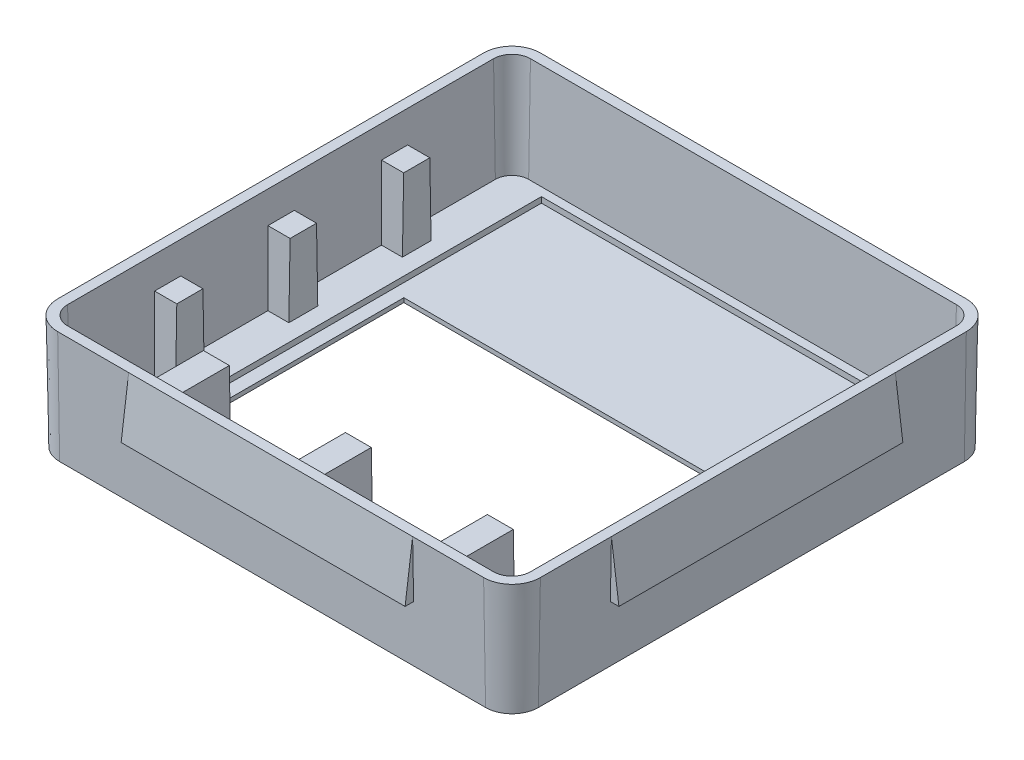
SolidWorks part; units mm, degrees
material "ABS"
ref_plane "Front Plane" through (0, 0, 0) normal (0, 0, 1) x (1, 0, 0)
ref_plane "Top Plane" through (0, 0, 0) normal (0, 1, 0) x (1, 0, 0)
ref_plane "Right Plane" through (0, 0, 0) normal (1, 0, 0) x (0, 0, -1)
sketch "Sketch1" plane through (0, 0, 0) normal (0, 1, 0) x (1, 0, 0)
  line L1 (-7.5, -8.5) -> (7.5, -8.5)
  line L2 (-8.5, -7.5) -> (-8.5, 7.5)
  line L3 (-7.5, 8.5) -> (7.5, 8.5)
  line L4 (8.5, -7.5) -> (8.5, 7.5)
  line L5 (-8.5, -8.5) -> (8.5, 8.5) construction
  line L6 (-8.5, 8.5) -> (8.5, -8.5) construction
  arc A0 (-8.5, 7.5) -> (-7.5, 8.5) centre (-7.5, 7.5) cw
  arc A1 (8.5, 7.5) -> (7.5, 8.5) centre (7.5, 7.5) ccw
  arc A2 (8.5, -7.5) -> (7.5, -8.5) centre (7.5, -7.5) cw
  arc A3 (-7.5, -8.5) -> (-8.5, -7.5) centre (-7.5, -7.5) cw
  point P0 (0, 0)
  dimension "D3" = 1
  dimension "D1" = 17
  dimension "D2" = 17
extrude "Boss-Extrude1" add sketch "Sketch1" against normal blind 4 draft 1
shell "Shell1" thickness 0.35 removed face at (0, 0, 0)
sketch "Sketch2" plane through (0, -4, 0) normal (0, -1, 0) x (1, 0, 0)
  line L0 (-7.5, 8.5) -> (7.5, 8.5) construction
  line L1 (-6.29, 4.5) -> (6.29, 4.5)
  line L2 (-6.29, 4.5) -> (-6.29, -2.48)
  line L3 (-6.29, -2.48) -> (6.29, -2.48)
  line L4 (6.29, 4.5) -> (6.29, -2.48)
  point P0 (0, 0)
  dimension "D1" = 4
  dimension "D2" = 6.98
extrude "Cut-Extrude1" cut sketch "Sketch2" against normal blind 2
sketch "Sketch3" plane through (0, -3.65, 0) normal (0, 1, 0) x (1, 0, 0)
  line L1 (6.75, 7.7862) -> (-6.75, 7.7862)
  line L2 (6.75, 7.7862) -> (6.75, -5.31)
  line L3 (6.75, -5.31) -> (-6.75, -5.31)
  line L4 (-6.75, 7.7862) -> (-6.75, -5.31)
  line L5 (6.29, 2.48) -> (6.29, -4.5) construction
  line L6 (-6.29, -4.5) -> (-6.29, 2.48) construction
  line L8 (6.29, -4.5) -> (-6.29, -4.5) construction
  line L9 (7.5, 8.0862) -> (-7.5, 8.0862) construction
  point P0 (0, 0)
  dimension "D1" = 0.81
  dimension "D2" = 0.46
  dimension "D3" = 0.46
  dimension "D4" = 0.3
extrude "Cut-Extrude2" cut sketch "Sketch3" against normal blind 0.2
ref_plane "Plane1" through (0, -1.2, 0) normal (0, -1, 0) x (-1, 0, 0)
ref_plane "Plane4" through (7.35, 0, 0) normal (-1, 0, 0) x (0, 0, 1)
sketch "Sketch11" plane through (7.35, 0, 0) normal (-1, 0, 0) x (0, 0, 1)
  line L0 (-9.35, -1.2) -> (9.35, -1.2) construction
  line L1 (-0.4555, -1.1) -> (0.4651, -1.1)
  line L3 (-0.5, -3.65) -> (0.5096, -3.65)
  line L5 (-7.5, -3.65) -> (7.5, -3.65) construction
  line L7 (0.5096, -3.65) -> (0.4651, -1.1)
  line L8 (-0.5, -3.65) -> (-0.4555, -1.1)
  dimension "D1" = 0.1
  dimension "D2" = 89
  dimension "D3" = 89
extrude "Boss-Extrude3" add sketch "Sketch11" against normal up to surface (0.7362 mm away) up to face at (8.1181, -1.825, 0)
ref_plane "Plane5" through (-7.35, 0, 0) normal (1, 0, 0) x (0, 0, -1)
sketch "Sketch13" plane through (-7.35, 0, 0) normal (1, 0, 0) x (0, 0, -1)
  line L0 (-9.35, -1.2) -> (9.35, -1.2) construction
  line L3 (-0.5, -3.65) -> (0.5096, -3.65)
  line L6 (0.5096, -3.65) -> (0.4651, -1.1)
  line L7 (-0.5, -3.65) -> (-0.4555, -1.1)
  line L8 (-0.4555, -1.1) -> (0.4651, -1.1)
  dimension "D1" = 0.1
  dimension "D2" = 89
  dimension "D3" = 89
extrude "Boss-Extrude4" add sketch "Sketch13" against normal up to surface (0.7362 mm away) up to face at (-8.1181, -1.825, 0)
ref_plane "Plane6" through (0, 0, 0) normal (1, 0, 0.0016) x (0.0016, 0, -1)
pattern_linear "LPattern2" count 2 spacing 4 along (0, 0, 1) of "Boss-Extrude3"
mirror "Mirror4" about plane through (0, 0, 0) normal (0, 0, 1) of "LPattern2"
pattern_linear "LPattern3" count 2 spacing 4 along (0, 0, 1) of "Boss-Extrude4"
mirror "Mirror5" about plane through (0, 0, 0) normal (0, 0, 1) of "LPattern3"
ref_plane "Plane7" through (0, 0, 5.41) normal (0, 0, 1) x (1, 0, 0)
sketch "Sketch16" plane through (0, 0, 5.41) normal (0, 0, 1) x (1, 0, 0)
  line L0 (-0.5, -3.65) -> (0.5, -3.65)
  line L1 (-7.5, -3.65) -> (7.5, -3.65) construction
  line L2 (0, -55) -> (0, 55) construction
  line L3 (-0.4555, -1.1) -> (0.4555, -1.1)
  line L5 (-0.5, -3.65) -> (-0.4555, -1.1)
  line L6 (0.5, -3.65) -> (0.4555, -1.1)
  line L7 (-9.35, -1.2) -> (9.35, -1.2) construction
  point P9 (0, -1.1)
  dimension "D1" = 0.5
  dimension "D2" = 0.5
  dimension "D3" = 89
  dimension "D4" = 89
  dimension "D5" = 0.1
extrude "Boss-Extrude5" add sketch "Sketch16" along normal up to surface (2.6762 mm away) up to face at (0, -1.825, 8.1181)
pattern_linear "LPattern4" count 2 spacing 5 along (1, 0, 0) of "Boss-Extrude5"
mirror "Mirror6" about plane through (0, 0, 0) normal (1, 0, 0) of "LPattern4"
sketch "Sketch17" plane through (0, 0, 0) normal (0, 0, 1) x (1, 0, 0)
  line L0 (-8.5, 0) -> (-8.4651, -2)
  line L1 (9.35, 0) -> (-9.35, 0) construction
  line L2 (-8.4302, -4) -> (-8.5, 0) construction
  line L3 (-8.4651, -2) -> (-8.7651, -2)
  line L4 (-8.7651, -2) -> (-8.5, 0)
  line L5 (-8.4302, -4) -> (-7.5, -4) construction
  line L6 (0, -2.2) -> (0, 2.2) construction
  line L7 (8.7651, -2) -> (8.5, 0)
  line L8 (8.4651, -2) -> (8.7651, -2)
  line L9 (8.5, 0) -> (8.4651, -2)
  dimension "D1" = 0.3
  dimension "D2" = 2
extrude "Boss-Extrude6" add sketch "Sketch17" along normal mid plane 10
sketch "Sketch18" plane through (0, 0, 0) normal (1, 0, 0) x (0, 0, -1)
  line L0 (8.5, 0) -> (8.4651, -2)
  line L1 (9.35, 0) -> (-9.35, 0) construction
  line L2 (8.4302, -4) -> (8.5, 0) construction
  line L3 (8.4651, -2) -> (8.7651, -2)
  line L4 (8.7651, -2) -> (8.5, 0)
  line L5 (7.5, -4) -> (8.4302, -4) construction
  line L6 (0, 2.2) -> (0, -2.2) construction
  line L7 (-8.7651, -2) -> (-8.5, 0)
  line L8 (-8.4651, -2) -> (-8.7651, -2)
  line L9 (-8.5, 0) -> (-8.4651, -2)
  dimension "D1" = 0.3
  dimension "D2" = 2
extrude "Boss-Extrude7" add sketch "Sketch18" along normal mid plane 10
